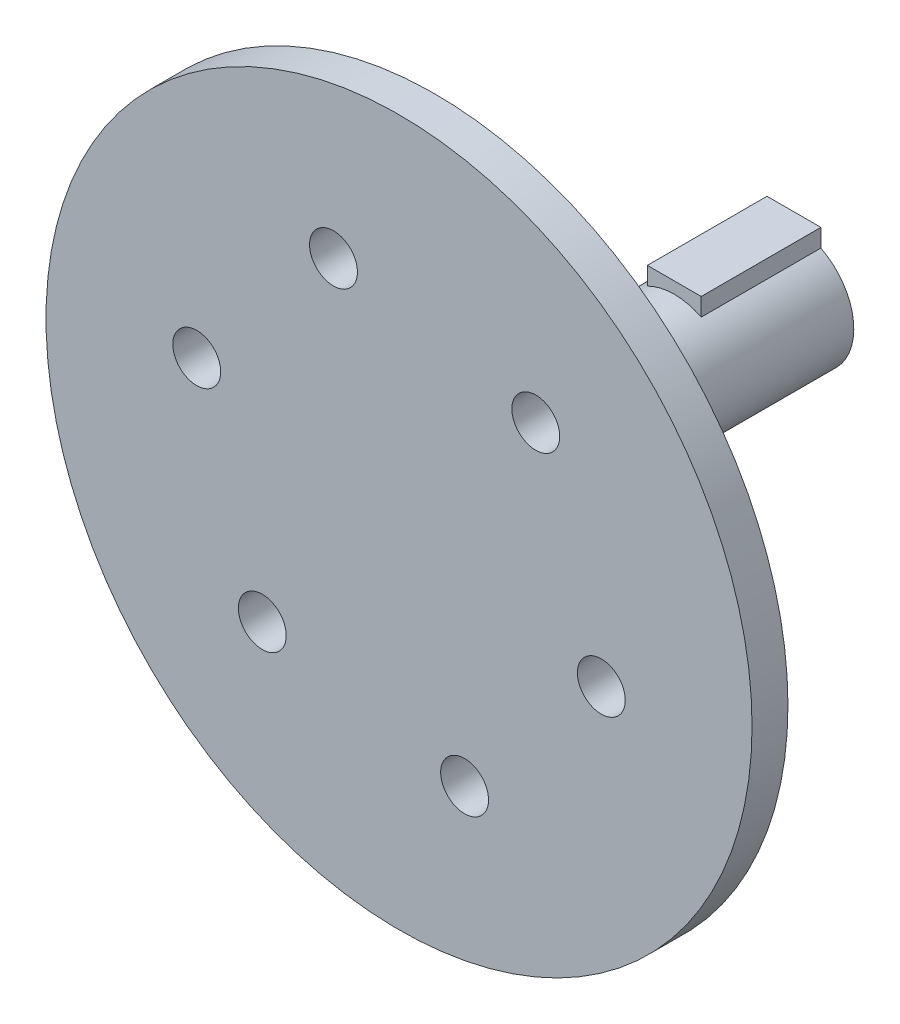
SolidWorks part; units mm, degrees
ref_plane "前视基准面" through (0, 0, 0) normal (0, 0, 1) x (1, 0, 0)
ref_plane "上视基准面" through (0, 0, 0) normal (0, 1, 0) x (1, 0, 0)
ref_plane "右视基准面" through (0, 0, 0) normal (1, 0, 0) x (0, 0, -1)
sketch "草图2" plane through (0, 0, 0) normal (0, 0, 1) x (1, 0, 0)
  line L1 (-2.25, 5.9651) -> (2.25, 5.9651)
  line L2 (-2.25, 5.9651) -> (-2.25, 4.4651)
  line L4 (2.25, 5.9651) -> (2.25, 4.4651)
  circle A1 centre (0, 0) radius 5
  point P2 (-2.1955, 4.4922)
  point P7 (2.2215, 4.4794)
  dimension "D1" = 4.5
  dimension "D2" = 1.5
  dimension "D3" = 4.5
  dimension "D4" = 1.5
extrude "凸台-拉伸1" add sketch "草图2" along normal blind 10 contours A1 | A1 L4 L1 L2 region at (0, 5.3845, 0) region at (0, 0, 0)
extrude "凸台-拉伸2" add sketch "草图2<3>" along normal blind 30 contours A1 region at (0, 0, 0)
sketch "草图2<3>" plane through (0, 0, 0) normal (0, 0, 1) x (1, 0, 0) same geometry as "草图2"
sketch "草图3" plane through (0, 0, 30) normal (0, 0, 1) x (1, 0, 0)
  circle A0 centre (0, 0) radius 29.5
extrude "凸台-拉伸3" add sketch "草图3" along normal blind 3
sketch "草图4" plane through (0, 0, 33) normal (0, 0, 1) x (1, 0, 0)
  circle A0 centre (-5.478, 16.3571) radius 2
  circle A1 centre (11.4267, 12.9226) radius 2
  circle A2 centre (16.9046, -3.4345) radius 2
  circle A3 centre (5.478, -16.3571) radius 2
  circle A4 centre (-11.4267, -12.9226) radius 2
  circle A5 centre (-16.9046, 3.4345) radius 2
  point P15 (0, 0)
  dimension "D1" = 17.25
  dimension "D2" = 6
extrude "切除-拉伸1" cut sketch "草图4" against normal blind 3
